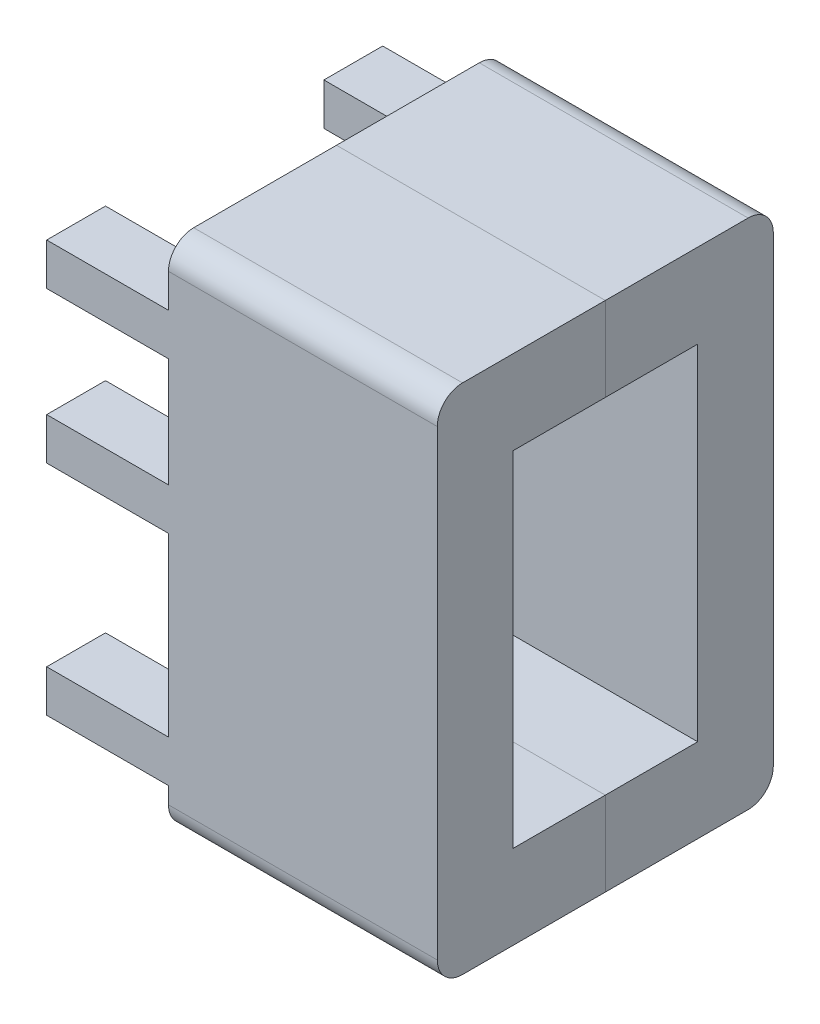
SolidWorks part; units mm, degrees
ref_plane "Alzado" through (0, 0, 0) normal (0, 0, 1) x (1, 0, 0)
ref_plane "Planta" through (0, 0, 0) normal (0, 1, 0) x (1, 0, 0)
ref_plane "Vista lateral" through (0, 0, 0) normal (1, 0, 0) x (0, 0, -1)
sketch "Croquis2" plane through (0, 0, 0) normal (1, 0, 0) x (0, 0, -1)
  line L0 (0, 24.489) -> (0, -53.3578) construction
  line L1 (5.835, 13.2874) -> (5.835, 12.9749) construction
  line L2 (10, 6.2874) -> (10, 3.7874) construction
  line L3 (5.835, -38.7126) -> (5.835, -38.4002) construction
  line L4 (5.835, -38.7126) -> (8, -38.7126) construction
  line L5 (9, -32.7126) -> (9, -37.7126) construction
  line L6 (10, -29.2126) -> (10, -31.7126) construction
  line L7 (5.835, 13.2874) -> (8, 13.2874) construction
  line L8 (9, 7.2874) -> (9, 12.2874) construction
  line L9 (6.5, 7.2874) -> (-6.5, 7.2874) construction
  line L10 (10, -29.2126) -> (10, 3.7874) construction
  line L11 (5.835, 13.2874) -> (5.835, 12.9749) construction
  line L12 (10, 6.2874) -> (10, 3.7874) construction
  line L13 (5.835, -38.7126) -> (5.835, -38.4002) construction
  line L14 (5.835, -38.7126) -> (8, -38.7126) construction
  line L15 (9, -32.7126) -> (9, -37.7126) construction
  line L16 (10, -29.2126) -> (10, -31.7126) construction
  line L17 (5.835, 13.2874) -> (8, 13.2874) construction
  line L18 (9, 7.2874) -> (9, 12.2874) construction
  line L19 (6.5, 7.2874) -> (-6.5, 7.2874) construction
  line L20 (10, -29.2126) -> (10, 3.7874) construction
  line L21 (-20, 17.7874) -> (20, 17.7874)
  line L22 (20, 17.7874) -> (20, -43.2126)
  line L24 (20, -43.2126) -> (-20, -43.2126)
  line L25 (-20, 17.7874) -> (-20, -43.2126)
  line L26 (-6.5, -32.7126) -> (6.5, -32.7126) construction
  line L27 (9, -32.7126) -> (6.5, -32.7126) construction
  line L28 (-6.5, -32.7126) -> (6.5, -32.7126) construction
  line L29 (9, -32.7126) -> (6.5, -32.7126) construction
  line L30 (-3, -33.7126) -> (-3, -32.7126) construction
  line L31 (3, -33.7126) -> (3, -32.7126) construction
  line L32 (-3, -33.7126) -> (-3, -32.7126) construction
  line L33 (3, -33.7126) -> (3, -32.7126) construction
  arc A0 (5.835, -38.4002) -> (4.335, -38.4002) centre (5.085, -36.3426) ccw construction
  arc A1 (4.335, 12.9749) -> (5.835, 12.9749) centre (5.085, 10.9174) ccw construction
  arc A2 (5.835, -38.4002) -> (4.335, -38.4002) centre (5.085, -36.3426) ccw construction
  arc A3 (4.335, 12.9749) -> (5.835, 12.9749) centre (5.085, 10.9174) ccw construction
  arc A4 (8, -38.7126) -> (9, -37.7126) centre (8, -37.7126) ccw construction
  arc A5 (9, -32.7126) -> (10, -31.7126) centre (9, -31.7126) ccw construction
  arc A6 (9, 12.2874) -> (8, 13.2874) centre (8, 12.2874) ccw construction
  arc A7 (10, 6.2874) -> (9, 7.2874) centre (9, 6.2874) ccw construction
  arc A8 (8, -38.7126) -> (9, -37.7126) centre (8, -37.7126) ccw construction
  arc A9 (9, -32.7126) -> (10, -31.7126) centre (9, -31.7126) ccw construction
  arc A10 (9, 12.2874) -> (8, 13.2874) centre (8, 12.2874) ccw construction
  arc A11 (10, 6.2874) -> (9, 7.2874) centre (9, 6.2874) ccw construction
  point P31 (0, -43.2126)
  point P33 (0, 17.7874)
  dimension "D1" = 4.5
  dimension "D2" = 10
  dimension "D3" = 4.5
extrude "Saliente-Extruir1" add sketch "Croquis2" against normal blind 32
sketch "Croquis4" plane through (0, 0, 0) normal (1, 0, 0) x (0, 0, -1)
  line L0 (3, -33.7126) -> (3, -32.7126) construction
  line L1 (-6.5, -32.7126) -> (6.5, -32.7126) construction
  line L2 (9, -32.7126) -> (6.5, -32.7126) construction
  line L3 (10, -29.2126) -> (10, -31.7126) construction
  line L4 (10, 6.2874) -> (10, 3.7874) construction
  line L5 (10, -29.2126) -> (10, 3.7874) construction
  line L6 (6.5, 7.2874) -> (-6.5, 7.2874) construction
  line L7 (0, 24.489) -> (0, -53.3578) construction
  line L8 (3, -33.7126) -> (3, -32.7126) construction
  line L9 (-6.5, -32.7126) -> (6.5, -32.7126) construction
  line L10 (9, -32.7126) -> (6.5, -32.7126) construction
  line L11 (10, -29.2126) -> (10, -31.7126) construction
  line L12 (10, 6.2874) -> (10, 3.7874) construction
  line L13 (10, -29.2126) -> (10, 3.7874) construction
  line L14 (6.5, 7.2874) -> (-6.5, 7.2874) construction
  line L15 (0, 24.489) -> (0, -53.3578) construction
  line L16 (-11, 7.7874) -> (11, 7.7874)
  line L17 (11, 7.7874) -> (11, -33.2126)
  line L19 (-11, 7.7874) -> (-11, -33.2126)
  line L35 (3, -33.7126) -> (2.5, -34.2126) construction
  line L43 (11, -33.2126) -> (-11, -33.2126)
  arc A0 (9, -32.7126) -> (10, -31.7126) centre (9, -31.7126) ccw construction
  arc A1 (9, -32.7126) -> (10, -31.7126) centre (9, -31.7126) ccw construction
  point P14 (0, -33.2126)
  point P20 (0, 7.7874)
  point P22 (0, -43.2126)
  dimension "D1" = 0.5
  dimension "D2" = 1
  dimension "D3" = 0.5
  dimension "D8" = 0.5
  dimension "D9" = 2.5
extrude "Cortar-Extruir1" cut sketch "Croquis4" against normal through all both and the other way through all
sketch "Croquis5" plane through (-32, 0, 0) normal (-1, 0, 0) x (0, 0, 1)
  line L0 (-9, 7.2874) -> (-9, 12.2874) construction
  line L1 (-9, -32.7126) -> (-9, -37.7126) construction
  line L2 (-5.835, -38.7126) -> (-8, -38.7126) construction
  line L3 (-5.835, 13.2874) -> (-8, 13.2874) construction
  line L4 (-9, 7.2874) -> (-9, 12.2874) construction
  line L5 (-9, -32.7126) -> (-9, -37.7126) construction
  line L6 (-5.835, -38.7126) -> (-8, -38.7126) construction
  line L7 (-5.835, 13.2874) -> (-8, 13.2874) construction
  line L8 (0, 24.489) -> (0, -53.3578) construction
  line L9 (0, 24.489) -> (0, -53.3578) construction
  line L10 (9.5, 13.7874) -> (-9.5, 13.7874)
  line L11 (-9.5, 13.7874) -> (-9.5, -39.2126)
  line L12 (-9.5, -39.2126) -> (9.5, -39.2126)
  line L13 (9.5, 13.7874) -> (9.5, -39.2126)
  arc A0 (-4.335, -38.4002) -> (-5.835, -38.4002) centre (-5.085, -36.3426) ccw construction
  arc A1 (-5.835, 12.9749) -> (-4.335, 12.9749) centre (-5.085, 10.9174) ccw construction
  arc A2 (-4.335, -38.4002) -> (-5.835, -38.4002) centre (-5.085, -36.3426) ccw construction
  arc A3 (-5.835, 12.9749) -> (-4.335, 12.9749) centre (-5.085, 10.9174) ccw construction
  point P21 (0, -39.2126)
  point P22 (0, 13.7874)
  dimension "D1" = 0.5
  dimension "D2" = 0.5
  dimension "D3" = 0.5
extrude "Cortar-Extruir2" cut sketch "Croquis5" against normal blind 8 and the other way through all
sketch "Croquis7" plane through (-24, 0, 0) normal (-1, 0, 0) x (0, 0, 1)
  line L4 (-9.5, 7.7874) -> (9.5, 7.7874)
  line L5 (9.5, 7.7874) -> (9.5, 13.7874)
  line L6 (9.5, 13.7874) -> (-9.5, 13.7874)
  line L7 (-9.5, 13.7874) -> (-9.5, 7.7874)
  line L8 (-9.5, 7.7874) -> (9.5, 7.7874)
  line L9 (9.5, 7.7874) -> (9.5, 13.7874)
  line L10 (9.5, 13.7874) -> (-9.5, 13.7874)
  line L11 (-9.5, 13.7874) -> (-9.5, 7.7874)
  line L12 (9.5, -33.2126) -> (-9.5, -33.2126)
  line L13 (-9.5, -33.2126) -> (-9.5, -39.2126)
  line L14 (-9.5, -39.2126) -> (9.5, -39.2126)
  line L15 (9.5, -39.2126) -> (9.5, -33.2126)
  line L16 (9.5, -33.2126) -> (-9.5, -33.2126)
  line L17 (-9.5, -33.2126) -> (-9.5, -39.2126)
  line L18 (-9.5, -39.2126) -> (9.5, -39.2126)
  line L19 (9.5, -39.2126) -> (9.5, -33.2126)
  dimension "D1" = 0
  dimension "D2" = 0
extrude "Saliente-Extruir2" add sketch "Croquis7" along normal up to surface (8 mm away) from offset 2.5 up to face at (-32, -12.7126, 0)
sketch "Croquis9" plane through (-32, 0, 0) normal (1, 0, 0) x (0, 0, -1)
  line L0 (-15.5, 3.7699) -> (-15.5, -40.4991) construction
  line L1 (-20, 10.7699) -> (-13, 10.7699)
  line L2 (100, 3.7699) -> (-100, 3.7699) construction
  line L3 (100, 12.7699) -> (-100, 12.7699) construction
  line L4 (-20, 17.7874) -> (-20, -43.2126) construction
  line L5 (-11, -33.2126) -> (-11, 7.7874) construction
  line L6 (-20, 17.7874) -> (-20, -43.2126) construction
  line L7 (-11, -33.2126) -> (-11, 7.7874) construction
  line L8 (0, 24.489) -> (0, -53.3578) construction
  line L9 (0, 24.489) -> (0, -53.3578) construction
  line L10 (-20, 5.7699) -> (-11, 5.7699) construction
  line L11 (-15.5, 3.7699) -> (-15.5, 12.7699) construction
  line L12 (-13, 5.7699) -> (-20, 5.7699)
  line L15 (-20, 5.7699) -> (-20, 10.7699)
  line L16 (-13, 10.7699) -> (-13, 5.7699)
  line L17 (-13, -7.2301) -> (-13, -12.2301)
  line L18 (-13, -12.2301) -> (-20, -12.2301)
  line L19 (-20, -12.2301) -> (-20, -7.2301)
  line L20 (-20, -7.2301) -> (-13, -7.2301)
  line L21 (-13, -33.2301) -> (-13, -38.2301)
  line L22 (-13, -38.2301) -> (-20, -38.2301)
  line L23 (-20, -38.2301) -> (-20, -33.2301)
  line L24 (-20, -33.2301) -> (-13, -33.2301)
  line L25 (13, -33.2301) -> (13, -38.2301)
  line L26 (13, -38.2301) -> (20, -38.2301)
  line L27 (20, -38.2301) -> (20, -33.2301)
  line L28 (20, -33.2301) -> (13, -33.2301)
  line L29 (13, -12.2301) -> (20, -12.2301)
  line L30 (13, -7.2301) -> (13, -12.2301)
  line L31 (20, -12.2301) -> (20, -7.2301)
  line L32 (20, -7.2301) -> (13, -7.2301)
  line L33 (13, 5.7699) -> (20, 5.7699)
  line L34 (13, 10.7699) -> (13, 5.7699)
  line L35 (20, 5.7699) -> (20, 10.7699)
  line L36 (20, 10.7699) -> (13, 10.7699)
  point P14 (-15.5, 5.7699)
  dimension "D1" = 7
  dimension "D2" = 5
  dimension "D3" = 2
  dimension "D4" = 18
  dimension "D5" = 44
extrude "Saliente-Extruir3" add sketch "Croquis9" against normal blind 14.5
fillet "Redondeo1" radius 3 4 edges at (-16, -43.2126, 20) (-16, -43.2126, -20) (-16, 17.7874, -20) (-16, 17.7874, 20)
sketch "Croquis10" plane through (0, 0, 20) normal (0, 0, 1) x (1, 0, 0)
  line L0 (0, 14.7874) -> (-32, 14.7874) construction
  line L1 (0, 14.7874) -> (-32, 14.7874) construction
split "Partir1" trim tools "Alzado" bodies to split 108 resulting bodies 106 107
